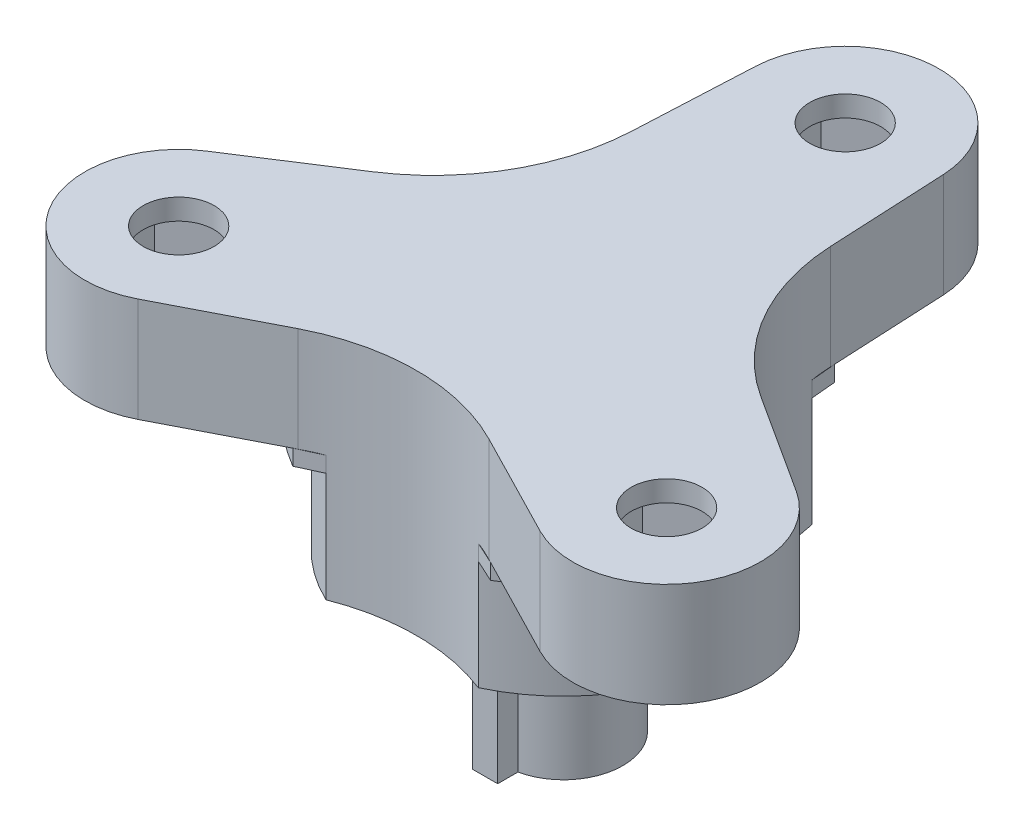
SolidWorks part; units mm, degrees
ref_plane "Ön Düzlem" through (0, 0, 0) normal (0, 0, 1) x (1, 0, 0)
ref_plane "Üst Düzlem" through (0, 0, 0) normal (0, 1, 0) x (1, 0, 0)
ref_plane "Sağ Düzlem" through (0, 0, 0) normal (1, 0, 0) x (0, 0, -1)
sketch "Sketch1" plane through (0, 0, 0) normal (0, 1, 0) x (1, 0, 0)
  line L0 (-4.4946, 13.7195) -> (-4.7723, 8.0342)
  line L1 (0, 13.5) -> (0, 0) construction
  line L2 (4.4946, 13.7195) -> (4.7723, 8.0342)
  line L3 (9.6341, -10.7522) -> (4.5717, -8.15)
  line L4 (14.1287, -2.9673) -> (9.3439, 0.1158)
  line L5 (-14.1287, -2.9673) -> (-9.3439, 0.1158)
  line L6 (-9.6341, -10.7522) -> (-4.5717, -8.15)
  circle A1 centre (0, 13.5) radius 1.7
  arc A3 (4.4946, 13.7195) -> (-4.4946, 13.7195) centre (0, 13.5) ccw
  circle A5 centre (0, 13.5) radius 4.5 construction
  circle A6 centre (11.6913, -6.75) radius 1.7
  arc A7 (9.6341, -10.7522) -> (14.1287, -2.9673) centre (11.6913, -6.75) ccw
  circle A8 centre (-11.6913, -6.75) radius 1.7
  arc A9 (-14.1287, -2.9673) -> (-9.6341, -10.7522) centre (-11.6913, -6.75) ccw
  circle A10 centre (0, 0) radius 5.8 construction
  arc A11 (-4.5717, -8.15) -> (4.5717, -8.15) centre (0, -17.0438) cw
  arc A12 (9.3439, 0.1158) -> (4.7723, 8.0342) centre (14.7604, 8.5219) cw
  arc A13 (-4.7723, 8.0342) -> (-9.3439, 0.1158) centre (-14.7604, 8.5219) cw
  point P27 (5.0229, 2.9)
  point P30 (0, 0)
  point P32 (-5.0229, 2.9)
  dimension "D2" = 3.4
  dimension "D3" = 11.6
  dimension "D7" = 10
  dimension "D4" = 4.5
  dimension "D1" = 13.5
  dimension "D6" = 3
extrude "Boss-Extrude1" add sketch "Sketch1" along normal blind 5
sketch "Sketch2" plane through (0, 5, 0) normal (0, 1, 0) x (1, 0, 0)
  line L0 (14.4413, -8.3377) -> (14.4413, -5.1623)
  line L1 (0, 16.6754) -> (-2.75, 15.0877)
  line L2 (-2.75, 15.0877) -> (-2.75, 11.9123)
  line L3 (-2.75, 11.9123) -> (0, 10.3246)
  line L4 (0, 10.3246) -> (2.75, 11.9123)
  line L5 (2.75, 11.9123) -> (2.75, 15.0877)
  line L6 (2.75, 15.0877) -> (0, 16.6754)
  line L7 (14.4413, -5.1623) -> (11.6913, -3.5746)
  line L8 (11.6913, -3.5746) -> (8.9413, -5.1623)
  line L9 (8.9413, -5.1623) -> (8.9413, -8.3377)
  line L10 (8.9413, -8.3377) -> (11.6913, -9.9254)
  line L11 (11.6913, -9.9254) -> (14.4413, -8.3377)
  line L12 (-14.4413, -8.3377) -> (-11.6913, -9.9254)
  line L13 (-11.6913, -9.9254) -> (-8.9413, -8.3377)
  line L14 (-8.9413, -8.3377) -> (-8.9413, -5.1623)
  line L15 (-8.9413, -5.1623) -> (-11.6913, -3.5746)
  line L16 (-11.6913, -3.5746) -> (-14.4413, -5.1623)
  line L17 (-14.4413, -5.1623) -> (-14.4413, -8.3377)
  circle A0 centre (0, 13.5) radius 2.75 construction
  point P24 (0, 0)
  dimension "D1" = 5.5
  dimension "D2" = 3
extrude "Cut-Extrude1" cut sketch "Sketch2" along normal blind 4 from surface starting at face at (0, 0, 0)
sketch "Sketch3" plane through (0, 0, 0) normal (0, -1, 0) x (1, 0, 0)
  circle A0 centre (0, 0) radius 2.5 construction
  dimension "D1" = 5
sketch "Sketch4" plane through (0, 0, 0) normal (0, -1, 0) x (1, 0, 0)
  arc A0 (-4.873, -7.0254) -> (4.873, -7.0254) centre (0, 0) ccw
  arc A1 (-3.6477, 7.7328) -> (-8.5207, -0.7074) centre (0, 0) ccw
  arc A2 (8.5207, -0.7074) -> (3.6477, 7.7328) centre (0, 0) ccw
  arc A3 (-4.7723, -8.0342) -> (-9.3439, -0.1158) centre (-14.7604, -8.5219) ccw construction
  arc A4 (-4.5717, 8.15) -> (4.5717, 8.15) centre (0, 17.0438) ccw construction
  arc A5 (9.3439, -0.1158) -> (4.7723, -8.0342) centre (14.7604, -8.5219) ccw construction
  arc A6 (-4.873, -7.0254) -> (-8.5207, -0.7074) centre (-14.7604, -8.5219) ccw
  arc A7 (-3.6477, 7.7328) -> (3.6477, 7.7328) centre (0, 17.0438) ccw
  arc A8 (8.5207, -0.7074) -> (4.873, -7.0254) centre (14.7604, -8.5219) ccw
  dimension "D1" = 17.1
extrude "Boss-Extrude2" add sketch "Sketch4" along normal blind 6
sketch "Sketch5" plane through (0, 0, 0) normal (0, -1, 0) x (1, 0, 0)
  line L0 (-9.6341, 10.7522) -> (-4.5717, 8.15) construction
  line L1 (-9.3439, -0.1158) -> (-14.1287, 2.9673) construction
  line L2 (-9.5, -0.0152) -> (-8.5207, -0.7074)
  line L3 (-4.7368, 8.2349) -> (-3.6477, 7.7328)
  line L4 (9.5, -0.0152) -> (8.5207, -0.7074)
  line L5 (4.7368, 8.2349) -> (3.6477, 7.7328)
  line L6 (-4.7632, -8.2196) -> (-4.873, -7.0254)
  line L7 (4.7632, -8.2196) -> (4.873, -7.0254)
  arc A0 (-4.873, -7.0254) -> (4.873, -7.0254) centre (0, 0) ccw construction
  arc A1 (8.5207, -0.7074) -> (3.6477, 7.7328) centre (0, 0) ccw construction
  arc A2 (-3.6477, 7.7328) -> (-8.5207, -0.7074) centre (0, 0) ccw construction
  arc A3 (-4.873, -7.0254) -> (4.873, -7.0254) centre (0, 0) ccw
  arc A4 (8.5207, -0.7074) -> (3.6477, 7.7328) centre (0, 0) ccw
  arc A5 (-3.6477, 7.7328) -> (-8.5207, -0.7074) centre (0, 0) ccw
  arc A6 (-4.7368, 8.2349) -> (-9.5, -0.0152) centre (0, 0) ccw
  arc A7 (9.5, -0.0152) -> (4.7368, 8.2349) centre (0, 0) ccw
  arc A8 (-4.7632, -8.2196) -> (4.7632, -8.2196) centre (0, 0) ccw
  point P24 (0, 0)
  dimension "D1" = 9.5
extrude "Boss-Extrude3" add sketch "Sketch5" along normal blind 0.75
sketch "Sketch6" plane through (0, -6, 0) normal (0, -1, 0) x (1, 0, 0)
  line L0 (-0.75, 2.9047) -> (-0.75, 3.9047) construction
  line L1 (0.75, 2.9047) -> (0.75, 3.9047) construction
  line L2 (-0.75, 3.4047) -> (0.75, 3.4047) construction
  line L3 (-0.75, 3.9047) -> (0.75, 3.9047) construction
  line L4 (0.6, 2.7861) -> (0.6, 3.7547)
  line L5 (-0.6, 3.7547) -> (0.6, 3.7547)
  line L6 (-0.6, 2.7861) -> (-0.6, 3.7547)
  arc A0 (-0.75, 2.9047) -> (0.75, 2.9047) centre (0, 0) ccw construction
  arc A1 (-0.6, 2.7861) -> (0.6, 2.7861) centre (0, 0) ccw
  point P9 (0, 3.4047)
  dimension "D1" = 6
  dimension "D2" = 1.5
  dimension "D3" = 1
  dimension "D4" = 0.15
extrude "Boss-Extrude4" add sketch "Sketch6" along normal blind 7.5
sketch "Sketch7" plane through (0, -13.5, 0) normal (0, -1, 0) x (1, 0, 0)
  circle A2 centre (0, 0) radius 1.3
  dimension "D1" = 2.6
extrude "Cut-Extrude2" cut sketch "Sketch7" against normal up to surface (7.5 mm away) up to face at (0, -6, 1.8614)
